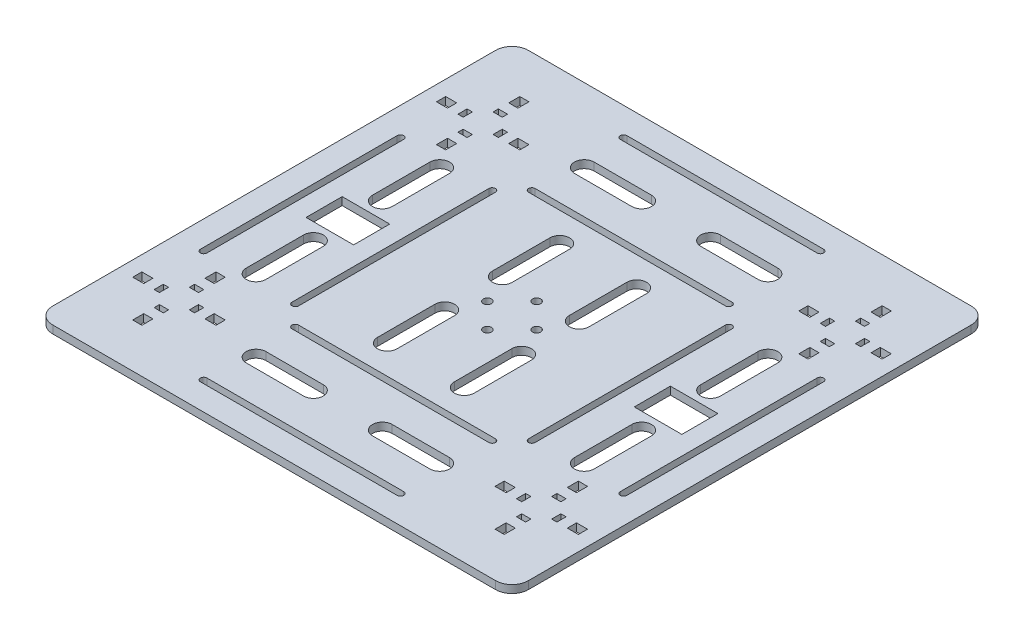
SolidWorks part; units mm, degrees
ref_plane "Front Plane" through (0, 0, 0) normal (0, 0, 1) x (1, 0, 0)
ref_plane "Top Plane" through (0, 0, 0) normal (0, 1, 0) x (1, 0, 0)
ref_plane "Right Plane" through (0, 0, 0) normal (1, 0, 0) x (0, 0, -1)
sketch "Sketch1" plane through (0, 0, 0) normal (0, 1, 0) x (1, 0, 0)
  line L1 (145, -145) -> (-145, -145)
  line L2 (145, -145) -> (145, 145)
  line L3 (145, 145) -> (-145, 145)
  line L4 (-145, -145) -> (-145, 145)
  line L5 (145, -145) -> (-145, 145) construction
  line L6 (145, 145) -> (-145, -145) construction
  point P0 (0, 0)
  dimension "D1" = 290
extrude "Boss-Extrude1" add sketch "Sketch1" along normal blind 4.7625
fillet "Fillet1" radius 10 4 edges at (145, 2.3813, -145) (-145, 2.3813, -145) (-145, 2.3813, 145) (145, 2.3813, 145)
sketch "Sketch3" plane through (0, 4.7625, 0) normal (0, 1, 0) x (1, 0, 0)
  line L0 (-145, 135) -> (-145, -135) construction
  line L1 (-113.25, 118) -> (-107.662, 118)
  line L2 (-113.25, 118) -> (-113.25, 111.269)
  line L3 (-113.25, 111.269) -> (-107.662, 111.269)
  line L4 (-107.662, 118) -> (-107.662, 111.269)
  line L5 (135, 145) -> (-135, 145) construction
  line L6 (-85.056, 95.394) -> (-91.787, 95.394)
  line L7 (-85.056, 95.394) -> (-85.056, 89.806)
  line L8 (-85.056, 89.806) -> (-91.787, 89.806)
  line L9 (-91.787, 95.394) -> (-91.787, 89.806)
  line L10 (-107.662, 67.2) -> (-107.662, 73.931)
  line L11 (-107.662, 67.2) -> (-113.25, 67.2)
  line L12 (-113.25, 67.2) -> (-113.25, 73.931)
  line L13 (-107.662, 73.931) -> (-113.25, 73.931)
  line L14 (-135.856, 89.806) -> (-129.125, 89.806)
  line L15 (-135.856, 89.806) -> (-135.856, 95.394)
  line L16 (-135.856, 95.394) -> (-129.125, 95.394)
  line L17 (-129.125, 89.806) -> (-129.125, 95.394)
  line L18 (-107.662, 104.925) -> (-113.25, 104.925)
  line L19 (-122.781, 95.394) -> (-119.581, 95.394)
  line L20 (-122.781, 95.394) -> (-122.781, 89.806)
  line L21 (-122.781, 89.806) -> (-119.581, 89.806)
  line L22 (-119.581, 95.394) -> (-119.581, 89.806)
  line L23 (-107.662, 104.925) -> (-107.662, 101.725)
  line L24 (-107.662, 101.725) -> (-113.25, 101.725)
  line L25 (-113.25, 104.925) -> (-113.25, 101.725)
  line L26 (-98.131, 89.806) -> (-98.131, 95.394)
  line L27 (-98.131, 89.806) -> (-101.331, 89.806)
  line L28 (-101.331, 89.806) -> (-101.331, 95.394)
  line L29 (-98.131, 95.394) -> (-101.331, 95.394)
  line L30 (-113.25, 80.275) -> (-107.662, 80.275)
  line L31 (-113.25, 80.275) -> (-113.25, 83.475)
  line L32 (-113.25, 83.475) -> (-107.662, 83.475)
  line L33 (-107.662, 80.275) -> (-107.662, 83.475)
  point P8 (-110.456, 92.6)
  point P9 (-110.456, 111.269)
  point P25 (-110.456, 92.6)
  point P42 (-110.456, 92.6)
  dimension "D1" = 5.588
  dimension "D2" = 6.731
  dimension "D3" = 31.75
  dimension "D4" = 27
  dimension "D5" = 25.4
  dimension "D7" = 3.2
  dimension "D8" = 13.075
  dimension "D6" = 4
  dimension "D9" = 4
extrude "Cut-Extrude1" cut sketch "Sketch3" against normal up to surface (4.7625 mm away) up to face at (0, 0, 0)
mirror "Mirror1" about plane through (0, 0, 0) normal (0, 0, 1) of "Cut-Extrude1"
mirror "Mirror2" about plane through (0, 0, 0) normal (1, 0, 0) of "Mirror1"
sketch "Sketch4" plane through (0, 4.7625, 0) normal (0, 1, 0) x (1, 0, 0)
  line L0 (-60, 128) -> (60, 128) construction
  line L1 (-60, 130) -> (60, 130)
  line L2 (-60, 126) -> (60, 126)
  line L3 (135, 145) -> (-135, 145) construction
  line L4 (-60, 72.12) -> (60, 72.12) construction
  line L5 (-60, 74.12) -> (60, 74.12)
  line L6 (-60, 70.12) -> (60, 70.12)
  line L7 (128, 60) -> (128, -60) construction
  line L8 (130, 60) -> (130, -60)
  line L9 (126, 60) -> (126, -60)
  line L10 (72.12, 60) -> (72.12, -60) construction
  line L11 (74.12, 60) -> (74.12, -60)
  line L12 (70.12, 60) -> (70.12, -60)
  line L13 (60, -128) -> (-60, -128) construction
  line L14 (60, -130) -> (-60, -130)
  line L15 (60, -126) -> (-60, -126)
  line L16 (60, -72.12) -> (-60, -72.12) construction
  line L17 (60, -74.12) -> (-60, -74.12)
  line L18 (60, -70.12) -> (-60, -70.12)
  line L19 (-128, -60) -> (-128, 60) construction
  line L20 (-130, -60) -> (-130, 60)
  line L21 (-126, -60) -> (-126, 60)
  line L22 (-72.12, -60) -> (-72.12, 60) construction
  line L23 (-74.12, -60) -> (-74.12, 60)
  line L24 (-70.12, -60) -> (-70.12, 60)
  arc A0 (-60, 130) -> (-60, 126) centre (-60, 128) ccw
  arc A1 (60, 126) -> (60, 130) centre (60, 128) ccw
  arc A2 (-60, 74.12) -> (-60, 70.12) centre (-60, 72.12) ccw
  arc A3 (60, 70.12) -> (60, 74.12) centre (60, 72.12) ccw
  arc A4 (130, 60) -> (126, 60) centre (128, 60) ccw
  arc A5 (126, -60) -> (130, -60) centre (128, -60) ccw
  arc A6 (74.12, 60) -> (70.12, 60) centre (72.12, 60) ccw
  arc A7 (70.12, -60) -> (74.12, -60) centre (72.12, -60) ccw
  arc A8 (60, -130) -> (60, -126) centre (60, -128) ccw
  arc A9 (-60, -126) -> (-60, -130) centre (-60, -128) ccw
  arc A10 (60, -74.12) -> (60, -70.12) centre (60, -72.12) ccw
  arc A11 (-60, -70.12) -> (-60, -74.12) centre (-60, -72.12) ccw
  arc A12 (-130, -60) -> (-126, -60) centre (-128, -60) ccw
  arc A13 (-126, 60) -> (-130, 60) centre (-128, 60) ccw
  arc A14 (-74.12, -60) -> (-70.12, -60) centre (-72.12, -60) ccw
  arc A15 (-70.12, 60) -> (-74.12, 60) centre (-72.12, 60) ccw
  point P2 (0, 128)
  point P9 (0, 72.12)
  point P22 (128, 0)
  point P27 (72.12, 0)
  point P36 (0, -128)
  point P41 (0, -72.12)
  point P50 (-128, 0)
  point P55 (-72.12, 0)
  point P62 (0, 0)
  dimension "D1" = 2
  dimension "D2" = 15
  dimension "D3" = 120
  dimension "D4" = 55.88
  dimension "D5" = 4
extrude "Cut-Extrude2" cut sketch "Sketch4" against normal up to surface (4.7625 mm away) up to face at (110.456, 0, -81.875)
sketch "Sketch5" plane through (0, 4.7625, 0) normal (0, 1, 0) x (1, 0, 0)
  line L0 (-126, -60) -> (-126, 60) construction
  line L1 (-114.56, 11) -> (-85.56, 11)
  line L2 (-114.56, 11) -> (-114.56, -11)
  line L3 (-114.56, -11) -> (-85.56, -11)
  line L4 (-85.56, 11) -> (-85.56, -11)
  line L5 (-126, -60) -> (-126, 60) construction
  line L6 (-74.12, 60) -> (-74.12, -60) construction
  line L7 (-74.12, 60) -> (-74.12, -60) construction
  line L8 (-74.12, 0) -> (-126, 0) construction
  line L9 (0, -145) -> (0, 145) construction
  line L10 (135, 145) -> (-135, 145) construction
  line L11 (114.56, -11) -> (85.56, -11)
  line L12 (85.56, 11) -> (85.56, -11)
  line L13 (114.56, 11) -> (85.56, 11)
  line L14 (114.56, 11) -> (114.56, -11)
  point P6 (-114.56, 0)
  point P7 (-126, 0)
  point P12 (-100.06, 0)
  point P13 (-100.06, 11)
  point P20 (0, 0)
  dimension "D1" = 29
  dimension "D2" = 22
extrude "Cut-Extrude3" cut sketch "Sketch5" against normal up to surface (4.7625 mm away) up to face at (0, 0, -128)
sketch "Sketch6" plane through (0, 4.7625, 0) normal (0, 1, 0) x (1, 0, 0)
  line L0 (-56, 100.06) -> (-21, 100.06) construction
  line L1 (-56, 106.06) -> (-21, 106.06)
  line L2 (-56, 94.06) -> (-21, 94.06)
  line L3 (21, 100.06) -> (56, 100.06) construction
  line L4 (21, 106.06) -> (56, 106.06)
  line L5 (21, 94.06) -> (56, 94.06)
  line L6 (-60, 126) -> (60, 126) construction
  line L7 (94.06, 56) -> (94.06, 21)
  line L8 (106.06, 56) -> (106.06, 21)
  line L9 (94.06, -21) -> (94.06, -56)
  line L10 (106.06, -21) -> (106.06, -56)
  line L11 (100.06, 56) -> (100.06, 21) construction
  line L12 (100.06, -21) -> (100.06, -56) construction
  line L13 (56, -94.06) -> (21, -94.06)
  line L14 (56, -106.06) -> (21, -106.06)
  line L15 (-21, -94.06) -> (-56, -94.06)
  line L16 (-21, -106.06) -> (-56, -106.06)
  line L17 (56, -100.06) -> (21, -100.06) construction
  line L18 (-21, -100.06) -> (-56, -100.06) construction
  line L19 (-94.06, -56) -> (-94.06, -21)
  line L20 (-106.06, -56) -> (-106.06, -21)
  line L21 (-94.06, 21) -> (-94.06, 56)
  line L22 (-106.06, 21) -> (-106.06, 56)
  line L23 (-100.06, -56) -> (-100.06, -21) construction
  line L24 (-100.06, 21) -> (-100.06, 56) construction
  line L25 (-60, 70.12) -> (60, 70.12) construction
  line L26 (-70.12, -60) -> (-70.12, 60) construction
  line L27 (-60, 70.12) -> (60, 70.12) construction
  line L28 (-70.12, -60) -> (-70.12, 60) construction
  line L29 (-23.4533, 52.56) -> (-23.4533, 17.56) construction
  line L32 (-17.4533, 52.56) -> (-17.4533, 17.56)
  line L33 (-29.4533, 52.56) -> (-29.4533, 17.56)
  line L34 (0, 70.12) -> (0, 0) construction
  line L35 (0, 0) -> (-70.12, 0) construction
  line L36 (23.4533, 52.56) -> (23.4533, 17.56) construction
  line L37 (17.4533, 52.56) -> (17.4533, 17.56)
  line L38 (29.4533, 52.56) -> (29.4533, 17.56)
  line L39 (-23.4533, -52.56) -> (-23.4533, -17.56) construction
  line L40 (-17.4533, -52.56) -> (-17.4533, -17.56)
  line L41 (-29.4533, -52.56) -> (-29.4533, -17.56)
  line L42 (23.4533, -52.56) -> (23.4533, -17.56) construction
  line L43 (17.4533, -52.56) -> (17.4533, -17.56)
  line L44 (29.4533, -52.56) -> (29.4533, -17.56)
  arc A0 (-56, 106.06) -> (-56, 94.06) centre (-56, 100.06) ccw
  arc A1 (-21, 94.06) -> (-21, 106.06) centre (-21, 100.06) ccw
  arc A2 (21, 106.06) -> (21, 94.06) centre (21, 100.06) ccw
  arc A3 (56, 94.06) -> (56, 106.06) centre (56, 100.06) ccw
  arc A4 (60, 126) -> (60, 130) centre (60, 128) ccw construction
  arc A5 (-60, 130) -> (-60, 126) centre (-60, 128) ccw construction
  arc A6 (106.06, 56) -> (94.06, 56) centre (100.06, 56) ccw
  arc A7 (94.06, 21) -> (106.06, 21) centre (100.06, 21) ccw
  arc A8 (106.06, -21) -> (94.06, -21) centre (100.06, -21) ccw
  arc A9 (94.06, -56) -> (106.06, -56) centre (100.06, -56) ccw
  arc A10 (56, -106.06) -> (56, -94.06) centre (56, -100.06) ccw
  arc A11 (21, -94.06) -> (21, -106.06) centre (21, -100.06) ccw
  arc A12 (-21, -106.06) -> (-21, -94.06) centre (-21, -100.06) ccw
  arc A13 (-56, -94.06) -> (-56, -106.06) centre (-56, -100.06) ccw
  arc A14 (-106.06, -56) -> (-94.06, -56) centre (-100.06, -56) ccw
  arc A15 (-94.06, -21) -> (-106.06, -21) centre (-100.06, -21) ccw
  arc A16 (-106.06, 21) -> (-94.06, 21) centre (-100.06, 21) ccw
  arc A17 (-94.06, 56) -> (-106.06, 56) centre (-100.06, 56) ccw
  arc A20 (-17.4533, 52.56) -> (-29.4533, 52.56) centre (-23.4533, 52.56) ccw
  arc A21 (-29.4533, 17.56) -> (-17.4533, 17.56) centre (-23.4533, 17.56) ccw
  arc A22 (17.4533, 52.56) -> (29.4533, 52.56) centre (23.4533, 52.56) cw
  arc A23 (29.4533, 17.56) -> (17.4533, 17.56) centre (23.4533, 17.56) cw
  arc A24 (-17.4533, -52.56) -> (-29.4533, -52.56) centre (-23.4533, -52.56) cw
  arc A25 (-29.4533, -17.56) -> (-17.4533, -17.56) centre (-23.4533, -17.56) cw
  arc A26 (17.4533, -52.56) -> (29.4533, -52.56) centre (23.4533, -52.56) ccw
  arc A27 (29.4533, -17.56) -> (17.4533, -17.56) centre (23.4533, -17.56) ccw
  point P2 (-38.5, 100.06)
  point P7 (38.5, 100.06)
  point P15 (62, 128)
  point P19 (62, 100.06)
  point P24 (-62, 128)
  point P25 (-62, 100.06)
  point P28 (-23.4533, 35.06)
  point P31 (100.06, 38.5)
  point P36 (100.06, -38.5)
  point P45 (38.5, -100.06)
  point P50 (-38.5, -100.06)
  point P59 (-100.06, -38.5)
  point P64 (-100.06, 38.5)
  point P71 (0, 0)
  point P82 (0, 35.06)
  point P86 (23.4533, 35.06)
  point P94 (-23.4533, -35.06)
  point P101 (23.4533, -35.06)
  dimension "D1" = 6
  dimension "D2" = 35
  dimension "D3" = 25.94
  dimension "D5" = 46.6667
  dimension "D4" = 4
extrude "Cut-Extrude4" cut sketch "Sketch6" against normal up to surface (4.7625 mm away) up to face at (-100.06, 0, 0)
sketch "Sketch7" plane through (0, 4.7625, 0) normal (0, 1, 0) x (1, 0, 0)
  circle A0 centre (0, 15) radius 2.5
  circle A1 centre (15, 0) radius 2.5
  circle A2 centre (0, -15) radius 2.5
  circle A3 centre (-15, 0) radius 2.5
  point P12 (0, 0)
  dimension "D1" = 5
  dimension "D2" = 15
  dimension "D3" = 4
extrude "Cut-Extrude5" cut sketch "Sketch7" against normal up to surface (4.7625 mm away) up to face at (38.5, 0, -100.06)
